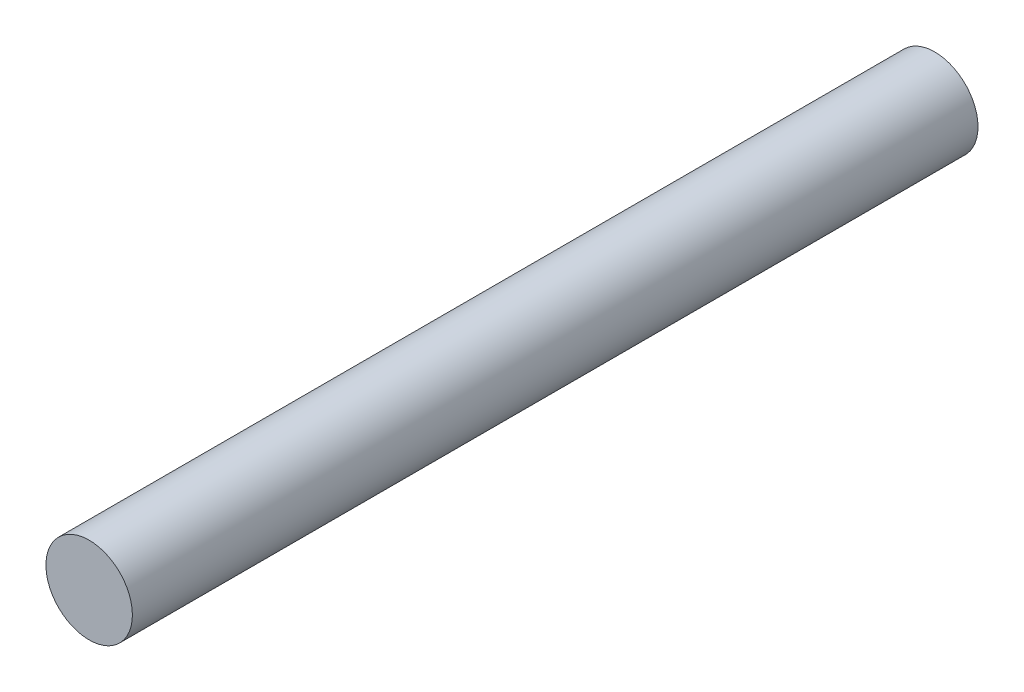
SolidWorks part; units mm, degrees
material "1060 Alloy"
ref_plane "Płaszczyzna przednia" through (0, 0, 0) normal (0, 0, 1) x (1, 0, 0)
ref_plane "Płaszczyzna górna" through (0, 0, 0) normal (0, 1, 0) x (1, 0, 0)
ref_plane "Płaszczyzna prawa" through (0, 0, 0) normal (1, 0, 0) x (0, 0, -1)
sketch "Sketch1" plane through (0, 0, 0) normal (0, 0, 1) x (1, 0, 0)
  circle A0 centre (0, 0) radius 10
  dimension "D1" = 20
extrude "Boss-Extrude1" add sketch "Sketch1" along normal blind 195.6
